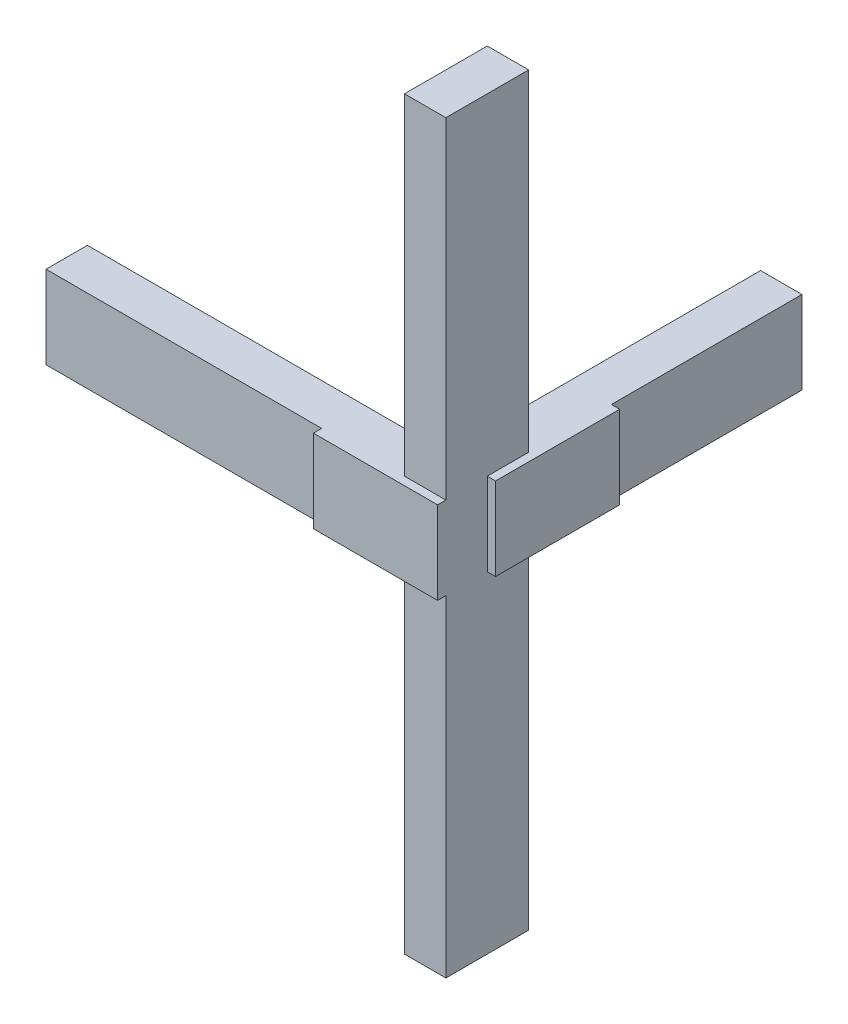
SolidWorks part; units mm, degrees
ref_plane "Front Plane" through (0, 0, 0) normal (0, 0, 1) x (1, 0, 0)
ref_plane "Top Plane" through (0, 0, 0) normal (0, 1, 0) x (1, 0, 0)
ref_plane "Right Plane" through (0, 0, 0) normal (1, 0, 0) x (0, 0, -1)
sketch "Sketch1" plane through (0, 0, 0) normal (0, 1, 0) x (1, 0, 0)
  line L0 (0, 0) -> (-173.1915, 0)
  line L1 (-173.1915, 0) -> (-173.1915, -20)
  line L2 (-173.1915, -20) -> (0, -20)
  line L3 (0, -20) -> (0, 0)
  line L4 (0, 0) -> (0, 20)
  line L5 (0, 20) -> (20, 20)
  line L6 (20, 20) -> (20, -20)
  line L7 (20, -20) -> (0, -20)
  line L8 (20, -20) -> (20, -24)
  line L9 (20, -24) -> (-40, -24)
  line L10 (-40, -24) -> (-40, -20)
  line L11 (0, 20) -> (0, 152.0626)
  line L12 (0, 152.0626) -> (20, 152.0626)
  line L13 (20, 152.0626) -> (20, 20)
  line L14 (20, 60) -> (24, 60)
  line L15 (24, 60) -> (24, 0)
  line L16 (24, 0) -> (20, 0)
  point P15 (24, 1.2406)
  dimension "D1" = 40
  dimension "D2" = 4
  dimension "D3" = 20
  dimension "D4" = 20
  dimension "D5" = 4
  dimension "D6" = 40
  dimension "D7" = 20
extrude "Boss-Extrude1" add sketch "Sketch1" along normal blind 40 contours L13 L12 L11 L5 | L16 L15 L14 L13 L6 | L7 L6 L5 L4 L3 | L2 L3 L0 L1 | L10 L9 L8 L7 L2 region at (-86.5957, 0, 10) region at (10, 0, 0) region at (-10, 0, 22) region at (10, 0, -86.0313) region at (22, 0, -30)
extrude "Boss-Extrude2" add sketch "Sketch1<3>" along normal blind 200 and the other way blind 160 contours L7 L6 L5 L4 L3 region at (10, 0, 0)
sketch "Sketch1<3>" plane through (0, 0, 0) normal (0, 1, 0) x (1, 0, 0) same geometry as "Sketch1"
